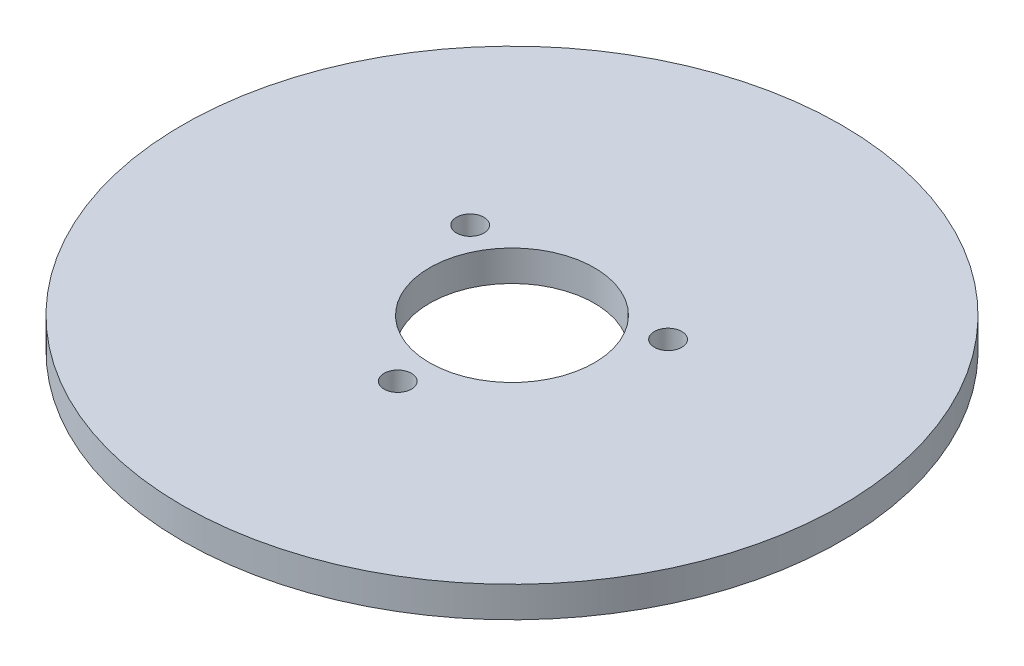
SolidWorks part; units mm, degrees
ref_plane "Front Plane" through (0, 0, 0) normal (0, 0, 1) x (1, 0, 0)
ref_plane "Top Plane" through (0, 0, 0) normal (0, 1, 0) x (1, 0, 0)
ref_plane "Right Plane" through (0, 0, 0) normal (1, 0, 0) x (0, 0, -1)
sketch "Sketch2" plane through (0, 0, 0) normal (0, 1, 0) x (1, 0, 0)
  circle A0 centre (0, 0) radius 19.05
extrude "Boss-Extrude1" add sketch "Sketch2" along normal blind 0.889 and the other way blind 0.889
sketch "Sketch4" plane through (0, 0.889, 0) normal (0, 1, 0) x (1, 0, 0)
  circle A0 centre (0, 0) radius 4.7625
extrude "Cut-Extrude1" cut sketch "Sketch4" against normal through all contours A0
sketch "Sketch5" plane through (0, -0.889, 0) normal (0, -1, 0) x (1, 0, 0)
  circle A0 centre (0, 6.604) radius 0.7938
  circle A1 centre (5.7192, -3.302) radius 0.7938
  circle A2 centre (-5.7192, -3.302) radius 0.7938
  point P9 (0, 0)
  dimension "D1" = 1.5875
  dimension "D2" = 6.604
  dimension "D3" = 0
  dimension "D4" = 3
extrude "Cut-Extrude2" cut sketch "Sketch5" against normal through all
